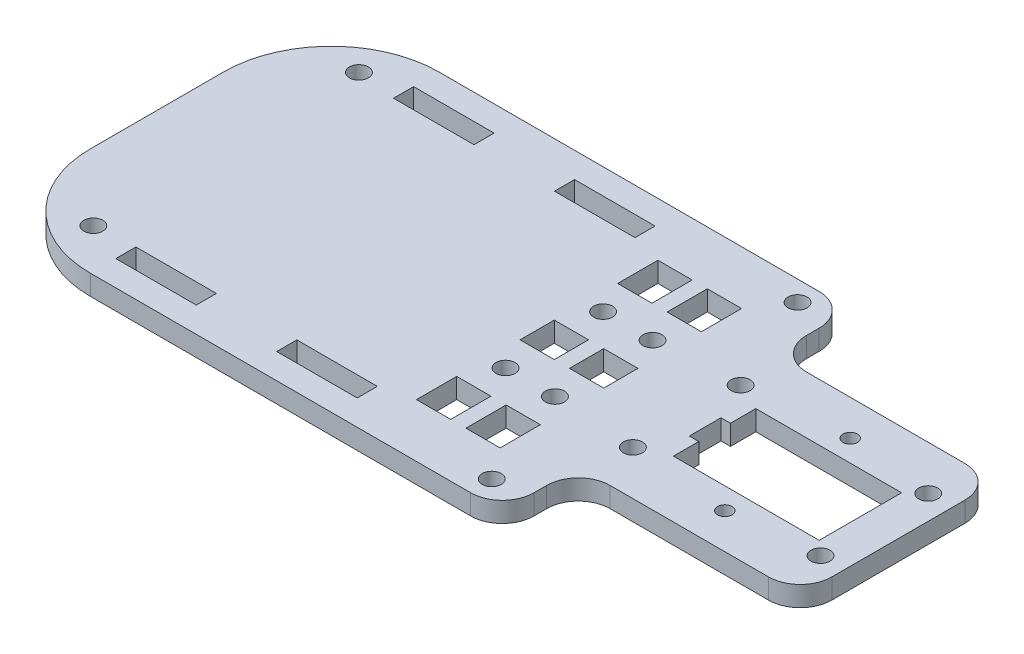
SolidWorks part; units mm, degrees
ref_plane "Front Plane" through (0, 0, 0) normal (0, 0, 1) x (1, 0, 0)
ref_plane "Top Plane" through (0, 0, 0) normal (0, 1, 0) x (1, 0, 0)
ref_plane "Right Plane" through (0, 0, 0) normal (1, 0, 0) x (0, 0, -1)
sketch "Sketch1" plane through (0, 0, 0) normal (0, 1, 0) x (1, 0, 0)
  line L0 (65.4, 40.2) -> (65.4, 14.8) construction
  line L1 (17, 0) -> (77, 0)
  line L2 (0, 17) -> (0, 38)
  line L3 (17, 55) -> (77, 55)
  line L4 (117, 17) -> (117, 38)
  line L5 (117, 27.5) -> (116.4302, 27.5) construction
  line L6 (60, 46.55) -> (65.4, 46.55)
  line L7 (60, 46.55) -> (60, 40.2)
  line L8 (60, 40.2) -> (65.4, 40.2)
  line L9 (65.4, 46.55) -> (65.4, 40.2)
  line L10 (60, 14.8) -> (65.4, 14.8)
  line L11 (60, 14.8) -> (60, 8.45)
  line L12 (60, 8.45) -> (65.4, 8.45)
  line L13 (65.4, 14.8) -> (65.4, 8.45)
  line L14 (65.4, 27.5) -> (47.2685, 27.5) construction
  line L15 (0, 27.5) -> (7.7524, 27.5) construction
  line L16 (62.7, 40.2) -> (62.7, 30.2) construction
  line L17 (65.4, 30.2) -> (60, 30.2)
  line L18 (65.4, 30.2) -> (65.4, 24.8)
  line L19 (65.4, 24.8) -> (60, 24.8)
  line L20 (60, 30.2) -> (60, 24.8)
  line L21 (62.7, 24.8) -> (62.7, 14.8) construction
  line L22 (67.8, 46.55) -> (73.2, 46.55)
  line L23 (67.8, 46.55) -> (67.8, 40.2)
  line L24 (67.8, 40.2) -> (73.2, 40.2)
  line L25 (73.2, 46.55) -> (73.2, 40.2)
  line L26 (67.8, 30.2) -> (73.2, 30.2)
  line L27 (67.8, 30.2) -> (67.8, 24.8)
  line L28 (67.8, 24.8) -> (73.2, 24.8)
  line L29 (73.2, 30.2) -> (73.2, 24.8)
  line L30 (67.8, 14.8) -> (73.2, 14.8)
  line L31 (67.8, 14.8) -> (67.8, 8.45)
  line L32 (67.8, 8.45) -> (73.2, 8.45)
  line L33 (73.2, 14.8) -> (73.2, 8.45)
  line L34 (70.5, 40.2) -> (70.5, 30.2) construction
  line L35 (70.5, 24.8) -> (70.5, 14.8) construction
  line L36 (60, 27.5) -> (65.4, 27.5) construction
  line L37 (73.2, 27.5) -> (67.8, 27.5) construction
  line L38 (55.1, 4) -> (55.1, 7.175)
  line L39 (17, 51) -> (29.7, 51)
  line L40 (17, 51) -> (17, 47.825)
  line L41 (17, 47.825) -> (29.7, 47.825)
  line L42 (29.7, 51) -> (29.7, 47.825)
  line L43 (42.4, 51) -> (55.1, 51)
  line L44 (42.4, 51) -> (42.4, 47.825)
  line L45 (42.4, 47.825) -> (55.1, 47.825)
  line L46 (55.1, 51) -> (55.1, 47.825)
  line L47 (42.4, 7.175) -> (55.1, 7.175)
  line L48 (42.4, 4) -> (42.4, 7.175)
  line L49 (42.4, 4) -> (55.1, 4)
  line L50 (29.7, 4) -> (29.7, 7.175)
  line L51 (17, 7.175) -> (29.7, 7.175)
  line L52 (17, 4) -> (17, 7.175)
  line L53 (17, 4) -> (29.7, 4)
  line L54 (88, 34) -> (111, 34)
  line L55 (88, 21) -> (111, 21)
  line L56 (111, 27.5) -> (86.5, 27.5) construction
  line L57 (86.5, 25) -> (88, 25)
  line L58 (88, 25) -> (88, 21)
  line L60 (82, 50) -> (82, 48)
  line L61 (87, 43) -> (112, 43)
  line L62 (87, 12) -> (112, 12)
  line L64 (111, 21) -> (111, 34)
  line L66 (82, 5) -> (82, 7)
  line L70 (88, 34) -> (88, 30)
  line L71 (88, 30) -> (86.5, 30)
  line L72 (86.5, 30) -> (86.5, 25)
  circle A0 centre (62.7, 35.2) radius 1.5
  circle A1 centre (70.5, 35.2) radius 1.5
  circle A2 centre (62.7, 19.8) radius 1.5
  circle A3 centre (70.5, 19.8) radius 1.5
  circle A4 centre (10.7398, 48.6273) radius 1.5
  circle A5 centre (10.7398, 6.7173) radius 1.5
  circle A6 centre (76.7798, 3.5423) radius 1.5
  circle A7 centre (76.7798, 51.8023) radius 1.5
  arc A8 (112, 43) -> (117, 38) centre (112, 38) cw
  circle A9 centre (83.6, 36) radius 1.5
  arc A10 (17, 0) -> (0, 17) centre (17, 17) cw
  arc A11 (0, 38) -> (17, 55) centre (17, 38) cw
  circle A12 centre (99.5, 37.4) radius 1.15
  circle A13 centre (99.5, 17.6) radius 1.15
  arc A14 (82, 48) -> (87, 43) centre (87, 48) ccw
  arc A15 (82, 50) -> (77, 55) centre (77, 50) ccw
  arc A16 (112, 12) -> (117, 17) centre (112, 17) ccw
  arc A17 (82, 7) -> (87, 12) centre (87, 7) cw
  arc A18 (82, 5) -> (77, 0) centre (77, 5) cw
  circle A19 centre (83.6, 19) radius 1.4999
  circle A20 centre (113.2, 19) radius 1.4999
  circle A21 centre (113.2, 36) radius 1.4999
  point P70 (10.7398, 48.6273)
  point P71 (10.7398, 6.7173)
  point P72 (76.7798, 51.8023)
  point P73 (76.7798, 3.5423)
  point P85 (117, 55)
  point P90 (0, 0)
  point P93 (0, 55)
  dimension "D19" = 3
  dimension "D20" = 3
  dimension "D21" = 3
  dimension "D22" = 3
  dimension "D34" = 3
  dimension "D35" = 3
  dimension "D36" = 3
  dimension "D37" = 3
  dimension "D38" = 12
  dimension "D39" = 2.3
  dimension "D43" = 5
  dimension "D44" = 17.5
  dimension "D1" = 117
  dimension "D2" = 0
  dimension "D3" = 55
  dimension "D4" = 5.4
  dimension "D5" = 5.4
  dimension "D6" = 6.35
  dimension "D7" = 6.35
  dimension "D8" = 38.1
  dimension "D9" = 17.5
  dimension "D10" = 60
  dimension "D11" = 5.4
  dimension "D12" = 5.4
  dimension "D13" = 2.4
  dimension "D14" = 2.4
  dimension "D15" = 2.4
  dimension "D16" = 5.4
  dimension "D17" = 5.4
  dimension "D18" = 5.4
  dimension "D23" = 0
  dimension "D24" = 0
  dimension "D25" = 12.7
  dimension "D26" = 12.7
  dimension "D27" = 12.7
  dimension "D28" = 17
  dimension "D29" = 4
  dimension "D30" = 4
  dimension "D31" = 3.175
  dimension "D32" = 3.175
  dimension "D33" = 6
  dimension "D40" = 9.9
  dimension "D41" = 11.5
  dimension "D42" = 35
  dimension "D45" = 15.9
  dimension "D46" = 15.9
  dimension "D47" = 8.5
  dimension "D48" = 8.5
  dimension "D49" = 8.5
  dimension "D50" = 8.5
  dimension "D51" = 13.7
  dimension "D52" = 13.7
  dimension "D53" = 13
  dimension "D54" = 6.5
  dimension "D55" = 23
  dimension "D56" = 23
  dimension "D57" = 24.5
extrude "Boss-Extrude1" add sketch "Sketch1" along normal blind 3.175
